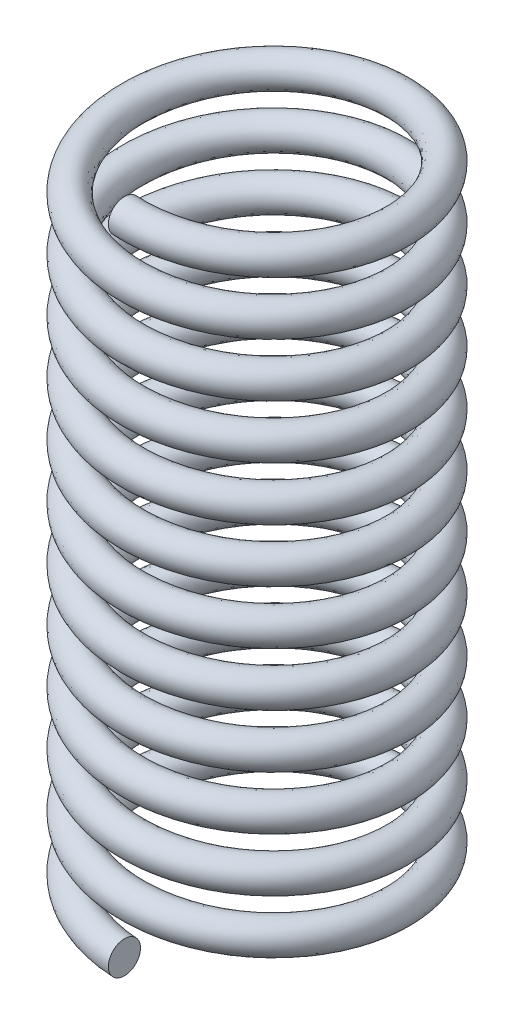
SolidWorks part; units mm, degrees
ref_plane "Front Plane" through (0, 0, 0) normal (0, 0, 1) x (1, 0, 0)
ref_plane "Top Plane" through (0, 0, 0) normal (0, 1, 0) x (1, 0, 0)
ref_plane "Right Plane" through (0, 0, 0) normal (1, 0, 0) x (0, 0, -1)
sketch "Sketch1" plane through (0, 0, 0) normal (1, 0, 0) x (0, 0, -1)
  circle A0 centre (0, 0) radius 0.4
  dimension "D1" = 0.8
sketch "Sketch2" plane through (0, 0, 0) normal (0, 1, 0) x (1, 0, 0)
  line L0 (0, 0) -> (0, 3.3) construction
  circle A0 centre (0, 3.3) radius 3.3
  dimension "D1" = 6.6
curve "Helix/Spiral1" pitch 1.3333 height 16 turns 12
sweep "Sweep1" add profiles "Sketch1" path "Helix/Spiral1"
sketch "Sketch3" plane through (0, 0, 0) normal (1, 0, 0) x (0, 0, -1)
  line L0 (0, 0) -> (3.3, 0) construction
  line L1 (3.3, 0) -> (3.3, 16) construction
  dimension "D1" = 3.3
  dimension "D2" = 16
